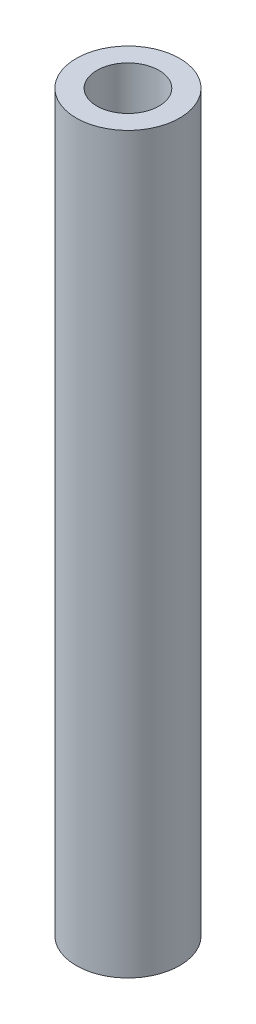
SolidWorks part; units mm, degrees
ref_plane "Front Plane" through (0, 0, 0) normal (0, 0, 1) x (1, 0, 0)
ref_plane "Top Plane" through (0, 0, 0) normal (0, 1, 0) x (1, 0, 0)
ref_plane "Right Plane" through (0, 0, 0) normal (1, 0, 0) x (0, 0, -1)
sketch "Sketch1" plane through (0, 0, 0) normal (0, 1, 0) x (1, 0, 0)
  circle A0 centre (0, 0) radius 1.5
  circle A1 centre (0, 0) radius 2.5
  dimension "D1" = 5
  dimension "D2" = 3
extrude "standoff" add sketch "Sketch1" along normal blind 35.5
